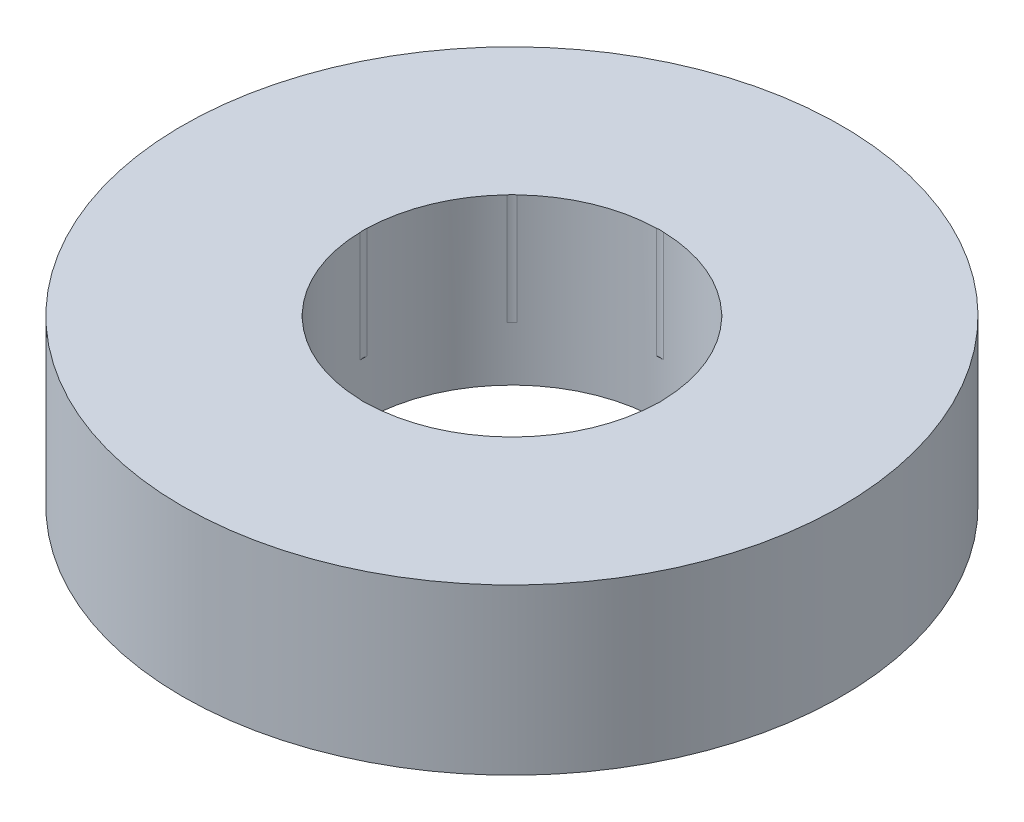
SolidWorks part; units mm, degrees
ref_plane "Front Plane" through (0, 0, 0) normal (0, 0, 1) x (1, 0, 0)
ref_plane "Top Plane" through (0, 0, 0) normal (0, 1, 0) x (1, 0, 0)
ref_plane "Right Plane" through (0, 0, 0) normal (1, 0, 0) x (0, 0, -1)
sketch "Sketch1" plane through (0, 0, 0) normal (0, 1, 0) x (1, 0, 0)
  circle A0 centre (0, 0) radius 50
  dimension "FLANGE_OD" = 100
extrude "Boss-Extrude1" add sketch "Sketch1" along normal blind 25
sketch "Sketch2" plane through (0, 0, 0) normal (0, 1, 0) x (1, 0, 0)
  circle A0 centre (0, 0) radius 22.5
  dimension "BORE_D" = 45
extrude "Cut-Extrude1" cut sketch "Sketch2" along normal through all
sketch "Sketch3" plane through (0, 25, 0) normal (0, 1, 0) x (1, 0, 0)
  circle A0 centre (0, 0) radius 19.1385 construction
  circle A1 centre (-19.1385, 0) radius 3.398
  dimension "BOLT_D" = 6.796
  dimension "BOLT_PCD" = 38.2771
extrude "Cut-Extrude2" cut sketch "Sketch3" against normal blind 16.7735
pattern_circular "CirPattern1" count 8 over 360 about axis through (0, 0, 0) along (0, 1, 0) of "Cut-Extrude2"
